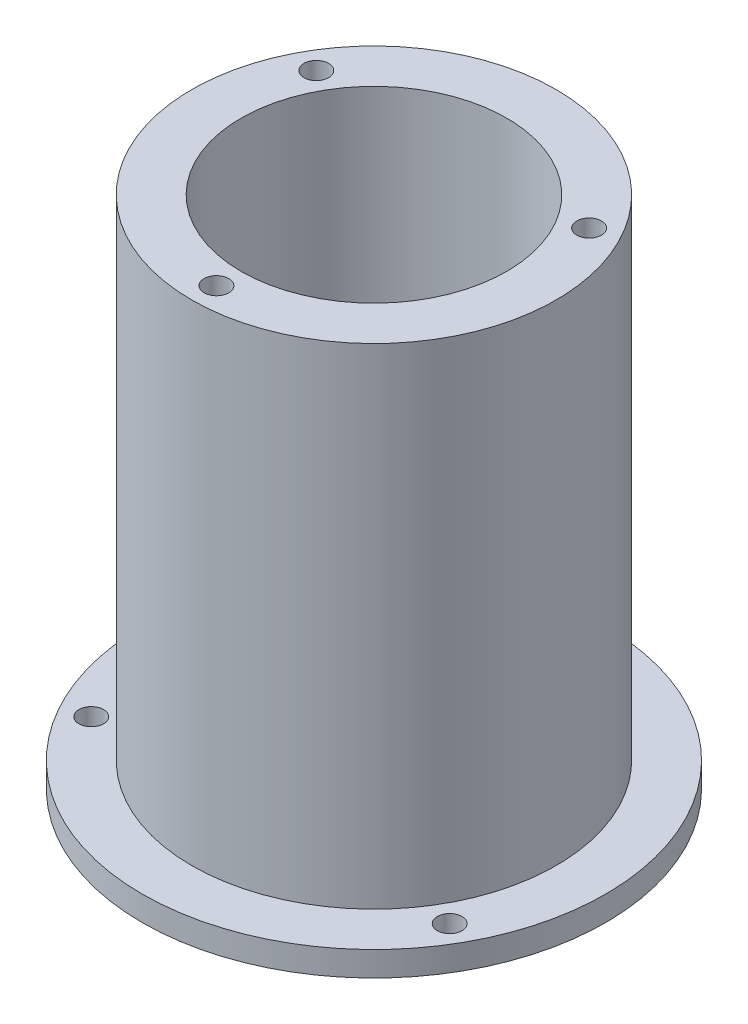
SolidWorks part; units mm, degrees
ref_plane "Front Plane" through (0, 0, 0) normal (0, 0, 1) x (1, 0, 0)
ref_plane "Top Plane" through (0, 0, 0) normal (0, 1, 0) x (1, 0, 0)
ref_plane "Right Plane" through (0, 0, 0) normal (1, 0, 0) x (0, 0, -1)
sketch "Sketch1" plane through (0, 0, 0) normal (0, 1, 0) x (1, 0, 0)
  circle A0 centre (0, 0) radius 37.5
  circle A1 centre (0, 0) radius 21.5
  dimension "D1" = 43
  dimension "D2" = 75
extrude "Boss-Extrude1" add sketch "Sketch1" along normal blind 4
sketch "Sketch2" plane through (0, 4, 0) normal (0, 1, 0) x (1, 0, 0)
  circle A0 centre (0, 0) radius 29.5
  circle A1 centre (0, 0) radius 21.5
  dimension "D1" = 59
  dimension "D2" = 43
extrude "Boss-Extrude2" add sketch "Sketch2" along normal blind 79.3
sketch "Sketch3" plane through (0, 4, 0) normal (0, 1, 0) x (1, 0, 0)
  circle A0 centre (0, 33.5) radius 2
  dimension "D1" = 33.5
  dimension "D2" = 4
extrude "Cut-Extrude1" cut sketch "Sketch3" against normal through all
pattern_circular "CirPattern1" count 3 over 360 about axis through (0, 4, 0) along (0, 1, 0) of "Cut-Extrude1"
sketch "Sketch4" plane through (0, 83.3, 0) normal (0, 1, 0) x (1, 0, 0)
  line L0 (0, 0) -> (0, 29.5)
  circle A0 centre (0, 0) radius 29.5 construction
  circle A1 centre (-22.0836, 12.75) radius 2
  dimension "D1" = 4
  dimension "D2" = 25.5
  dimension "D3" = 60
extrude "Cut-Extrude2" cut sketch "Sketch4" against normal blind 6 contours A1 region at (-22.0836, 83.3, -12.75)
pattern_circular "CirPattern2" count 3 over 360 about axis through (0, 83.3, 0) along (0, 1, 0) of "Cut-Extrude2"
